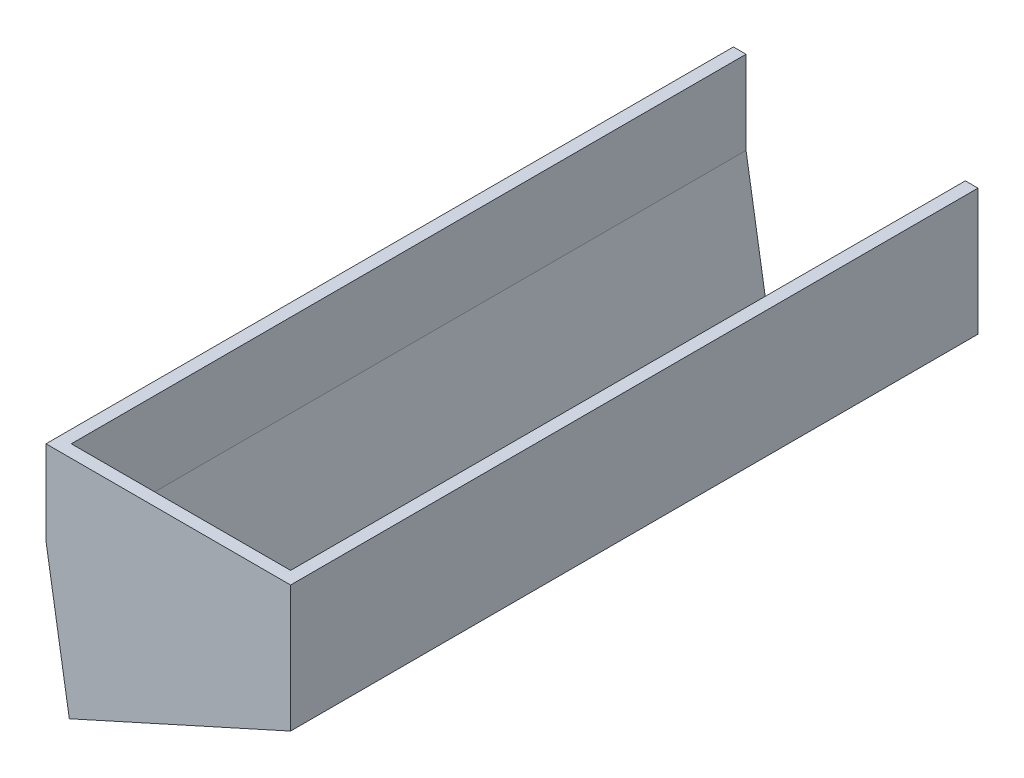
SolidWorks part; units mm, degrees
ref_plane "Front Plane" through (0, 0, 0) normal (0, 0, 1) x (1, 0, 0)
ref_plane "Top Plane" through (0, 0, 0) normal (0, 1, 0) x (1, 0, 0)
ref_plane "Right Plane" through (0, 0, 0) normal (1, 0, 0) x (0, 0, -1)
sketch "Sketch1" plane through (0, 0, 0) normal (0, 0, 1) x (1, 0, 0)
  line L0 (0, 0) -> (0, -19.7557)
  line L1 (0, -19.7557) -> (4.8532, -49.3606)
  line L2 (4.8532, -49.3606) -> (52, -28.0633)
  line L5 (-3, 0) -> (-3, -20)
  line L6 (-3, -20) -> (2.5252, -53.7041)
  line L7 (2.5252, -53.7041) -> (55, -30)
  line L10 (-3, 0) -> (0, 0)
  line L12 (52, -28.0633) -> (52, 0)
  line L13 (52, -28.0633) -> (52, 36.7789) construction
  line L14 (52, 36.7789) -> (67.0297, -2.1736) construction
  line L15 (55, -30) -> (55, 20.67) construction
  line L16 (55, 20.67) -> (64.2308, -3.2535) construction
  line L17 (52, 0) -> (55, 0)
  line L18 (55, 0) -> (55, -30)
  dimension "D2" = 20
  dimension "D3" = 30
  dimension "D4" = 30
  dimension "D5" = 3
  dimension "D6" = 52
  dimension "D7" = 75
  dimension "D1" = 3
extrude "Boss-Extrude1" add sketch "Sketch1" along normal blind 160
sketch "Sketch2" plane through (0, 0, 0) normal (0, 1, 0) x (1, 0, 0)
  line L0 (52, -160) -> (4.8532, -160) construction
  line L1 (49.8532, -8) -> (4.8532, -8)
  line L2 (49.8532, -8) -> (49.8532, -50)
  line L3 (49.8532, -50) -> (4.8532, -50)
  line L4 (4.8532, -8) -> (4.8532, -50)
  line L5 (49.8532, -63) -> (4.8532, -63)
  line L6 (49.8532, -63) -> (49.8532, -105)
  line L7 (49.8532, -105) -> (4.8532, -105)
  line L8 (4.8532, -63) -> (4.8532, -105)
  line L9 (49.8532, -118) -> (4.8532, -118)
  line L10 (49.8532, -118) -> (49.8532, -160)
  line L11 (49.8532, -160) -> (4.8532, -160)
  line L12 (4.8532, -118) -> (4.8532, -160)
  line L13 (4.8532, -160) -> (4.8532, 0) construction
  dimension "D1" = 42
  dimension "D2" = 13
  dimension "D3" = 42
  dimension "D4" = 13
  dimension "D5" = 42
  dimension "D6" = 45
extrude "Cut-Extrude1" cut sketch "Sketch2" against normal through all
sketch "Sketch3" plane through (0, 0, 160) normal (0, 0, 1) x (1, 0, 0)
  line L0 (-3, 0) -> (55, 0)
  line L1 (55, 0) -> (55, -30)
  line L2 (55, -30) -> (4.8532, -52.6525)
  line L9 (4.8532, -52.6525) -> (4.8532, -49.3606)
  line L10 (0, 0) -> (-3, 0)
  line L11 (-3, 0) -> (-3, -20)
  line L12 (-3, -20) -> (2.5252, -53.7041)
  line L13 (2.5252, -53.7041) -> (4.8532, -52.6525)
  line L18 (4.8532, -49.3606) -> (0, -19.7557)
  line L19 (0, -19.7557) -> (0, 0)
  line L21 (-3, 0) -> (-3, -20)
  line L22 (-3, -20) -> (2.5252, -53.7041)
  line L23 (2.5252, -53.7041) -> (4.8532, -52.6525)
  dimension "D1" = 0
extrude "Boss-Extrude2" add sketch "Sketch3" along normal blind 3
